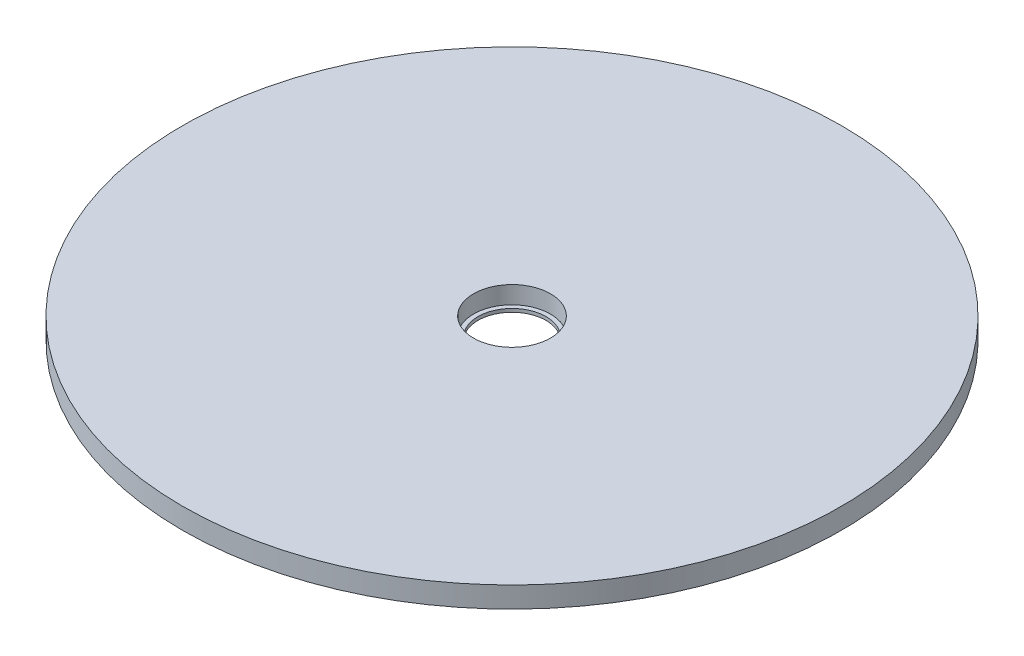
SolidWorks part; units mm, degrees
ref_plane "Front Plane" through (0, 0, 0) normal (0, 0, 1) x (1, 0, 0)
ref_plane "Top Plane" through (0, 0, 0) normal (0, 1, 0) x (1, 0, 0)
ref_plane "Right Plane" through (0, 0, 0) normal (1, 0, 0) x (0, 0, -1)
sketch "Sketch1" plane through (0, 0, 0) normal (0, 1, 0) x (1, 0, 0)
  circle A0 centre (0, 0) radius 150
extrude "Boss-Extrude1" add sketch "Sketch1" along normal blind 9.52
sketch "Sketch2" plane through (0, 9.52, 0) normal (0, 1, 0) x (1, 0, 0)
  circle A0 centre (0, 0) radius 15.5
extrude "Cut-Extrude1" cut sketch "Sketch2" against normal through all
sketch "Sketch3" plane through (0, 9.52, 0) normal (0, 1, 0) x (1, 0, 0)
  circle A0 centre (0, 0) radius 17.505
extrude "Cut-Extrude2" cut sketch "Sketch3" against normal blind 8
